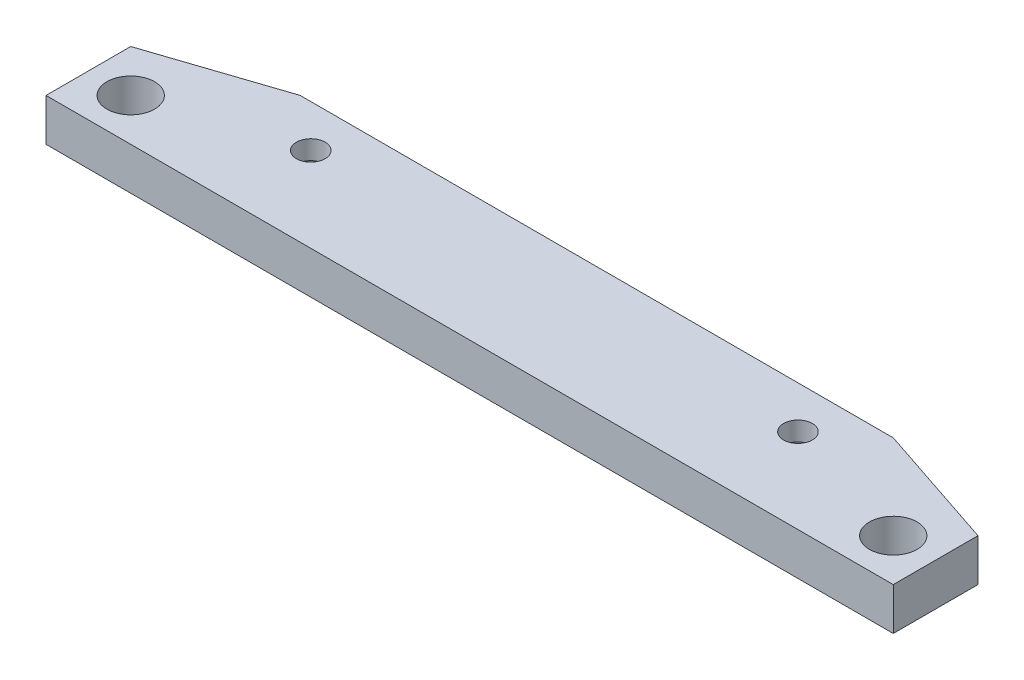
SolidWorks part; units mm, degrees
ref_plane "Front Plane" through (0, 0, 0) normal (0, 0, 1) x (1, 0, 0)
ref_plane "Top Plane" through (0, 0, 0) normal (0, 1, 0) x (1, 0, 0)
ref_plane "Right Plane" through (0, 0, 0) normal (1, 0, 0) x (0, 0, -1)
sketch "Sketch1" plane through (0, 0, 0) normal (0, 1, 0) x (1, 0, 0)
  line L0 (-12.7, 0) -> (101.6, 0) construction
  line L1 (0, 0) -> (88.9, 0)
  line L2 (0, 0) -> (0, 12.7)
  line L3 (0, 12.7) -> (88.9, 12.7)
  line L4 (88.9, 0) -> (88.9, 12.7)
  line L5 (-19.05, -6.35) -> (107.95, -6.35)
  line L6 (-19.05, -6.35) -> (-19.05, 6.35)
  line L7 (-19.05, 6.35) -> (107.95, 6.35)
  line L8 (107.95, -6.35) -> (107.95, 6.35)
  line L9 (80.9625, 6.35) -> (7.9375, 6.35) construction
  line L10 (44.45, 12.7) -> (44.45, 0) construction
  line L11 (44.45, -6.35) -> (44.45, 6.35) construction
  line L12 (-19.05, 6.35) -> (0, 12.7)
  line L13 (88.9, 12.7) -> (107.95, 6.35)
  line L14 (0, 12.7) -> (-19.05, 6.35)
  line L15 (-19.05, -6.35) -> (107.95, -6.35)
  line L16 (107.95, 6.35) -> (88.9, 12.7)
  point P17 (44.45, 0)
  point P18 (44.45, 6.35)
  point P20 (44.45, 0)
  dimension "D1" = 73.025
  dimension "D2" = 88.9
  dimension "D3" = 12.7
  dimension "D4" = 12.7
  dimension "D5" = 114.3
  dimension "D6" = 127
  dimension "D7" = 6.35
extrude "Boss-Extrude1" add sketch "Sketch1" along normal blind 6.35 contours L12 L3 L13 L8 L5 L6
sketch "Sketch11" plane through (0, 0, 0) normal (0, -1, 0) x (1, 0, 0)
  line L0 (-19.05, -6.35) -> (107.95, -6.35) construction
  line L1 (107.95, 6.35) -> (107.95, -6.35) construction
  line L2 (88.9, -12.7) -> (107.95, -6.35) construction
  line L3 (107.95, -6.35) -> (88.9, -12.7) construction
  line L4 (-19.05, 6.35) -> (-19.05, -6.35) construction
  line L5 (-19.05, -6.35) -> (0, -12.7) construction
  line L6 (0, -12.7) -> (-19.05, -6.35) construction
  line L7 (-19.05, 6.35) -> (107.95, 6.35) construction
  line L8 (-19.05, 6.35) -> (107.95, 6.35) construction
  line L9 (0, -12.7) -> (88.9, -12.7) construction
  line L10 (88.9, 0) -> (88.9, -12.7) construction
  line L11 (0, 0) -> (88.9, 0) construction
  line L12 (0, 0) -> (0, -12.7) construction
  line L13 (-19.05, -6.35) -> (107.95, -6.35)
  line L14 (107.95, 6.35) -> (107.95, -6.35)
  line L15 (88.9, -12.7) -> (107.95, -6.35)
  line L16 (107.95, -6.35) -> (88.9, -12.7)
  line L17 (-19.05, 6.35) -> (-19.05, -6.35)
  line L18 (-19.05, -6.35) -> (0, -12.7)
  line L19 (0, -12.7) -> (-19.05, -6.35)
  line L20 (-19.05, 6.35) -> (107.95, 6.35)
  line L21 (-19.05, 6.35) -> (107.95, 6.35)
  line L22 (0, -12.7) -> (88.9, -12.7)
  line L23 (88.9, 0) -> (88.9, -12.7)
  line L24 (0, 0) -> (88.9, 0)
  line L25 (0, 0) -> (0, -12.7)
  line L26 (44.45, -12.7) -> (44.45, 6.35) construction
  point P8 (101.6, 0)
  point P15 (-12.7, 0)
  dimension "D1" = 57.15
hole_wizard "1/4 Clearance Hole2" positions "Sketch12" profile "Sketch13" hole size "1/4" standard "ANSI Inch" end condition up to next
sketch "Sketch12" plane through (0, 0, 0) normal (0, -1, 0) x (-1, 0, 0)
  point P0 (-101.6, 0)
  point P3 (12.7, 0)
sketch "Sketch13" plane through (101.6, 0, 0) normal (1, 0, 0) x (0, 0, -1)
  line L0 (0, 0) -> (0, 6.35)
  line L1 (0, 6.35) -> (3.5712, 6.35)
  line L2 (3.5712, 6.35) -> (3.5712, 0)
  line L5 (3.5712, 0) -> (0, 0)
  line L11 (0, -6.35) -> (0, 107.95) construction
  dimension "Thru Hole Dia." = 7.1425
  dimension "Thru Hole Depth" = 6.35
sketch "Sketch14" plane through (0, 0, 0) normal (0, -1, 0) x (1, 0, 0)
  line L0 (-19.05, -6.35) -> (0, -12.7) construction
  line L1 (0, -12.7) -> (-19.05, -6.35) construction
  line L2 (0, -12.7) -> (88.9, -12.7) construction
  line L3 (88.9, 0) -> (88.9, -12.7) construction
  line L4 (0, 0) -> (88.9, 0) construction
  line L5 (0, 0) -> (0, -12.7) construction
  line L6 (-19.05, 6.35) -> (-19.05, -6.35) construction
  line L7 (-19.05, 6.35) -> (107.95, 6.35) construction
  line L8 (-19.05, 6.35) -> (107.95, 6.35) construction
  line L9 (88.9, -12.7) -> (107.95, -6.35) construction
  line L10 (107.95, -6.35) -> (88.9, -12.7) construction
  line L11 (107.95, 6.35) -> (107.95, -6.35) construction
  line L12 (-19.05, -6.35) -> (107.95, -6.35) construction
  line L13 (-19.05, -6.35) -> (0, -12.7)
  line L14 (0, -12.7) -> (-19.05, -6.35)
  line L15 (0, -12.7) -> (88.9, -12.7)
  line L16 (88.9, 0) -> (88.9, -12.7)
  line L17 (0, 0) -> (88.9, 0)
  line L18 (0, 0) -> (0, -12.7)
  line L19 (-19.05, 6.35) -> (-19.05, -6.35)
  line L20 (-19.05, 6.35) -> (107.95, 6.35)
  line L21 (-19.05, 6.35) -> (107.95, 6.35)
  line L22 (88.9, -12.7) -> (107.95, -6.35)
  line L23 (107.95, -6.35) -> (88.9, -12.7)
  line L24 (107.95, 6.35) -> (107.95, -6.35)
  line L25 (-19.05, -6.35) -> (107.95, -6.35)
  line L26 (44.45, -12.7) -> (44.45, 6.35) construction
  line L27 (44.45, -12.7) -> (44.45, 6.35) construction
  point P6 (80.9625, -6.35)
  point P15 (7.9375, -6.35)
  dimension "D1" = 36.5125
hole_wizard "CBORE for #6 Socket Head Cap Screw1" positions "Sketch15" profile "Sketch16" counterbore size "#6" standard "ANSI Inch" end condition up to next
sketch "Sketch15" plane through (0, 0, 0) normal (0, -1, 0) x (-1, 0, 0)
  point P0 (-80.9625, 6.35)
  point P3 (-7.9375, 6.35)
sketch "Sketch16" plane through (80.9625, 0, -6.35) normal (1, 0, 0) x (0, 0, -1)
  line L0 (0, 0) -> (0, 6.35)
  line L1 (0, 6.35) -> (2.1526, 6.35)
  line L3 (2.1526, 6.35) -> (2.1527, 3.5052)
  line L4 (2.1527, 3.5052) -> (3.5725, 3.5052)
  line L5 (3.5725, 3.5052) -> (3.5725, 0)
  line L7 (3.5725, 0) -> (0, 0)
  line L11 (0, -6.35) -> (0, 107.95) construction
  dimension "Thru Hole Dia." = 4.3053
  dimension "Thru Hole Depth" = 6.35
  dimension "C'Bore Dia." = 7.145
  dimension "C'Bore Depth" = 3.5052
